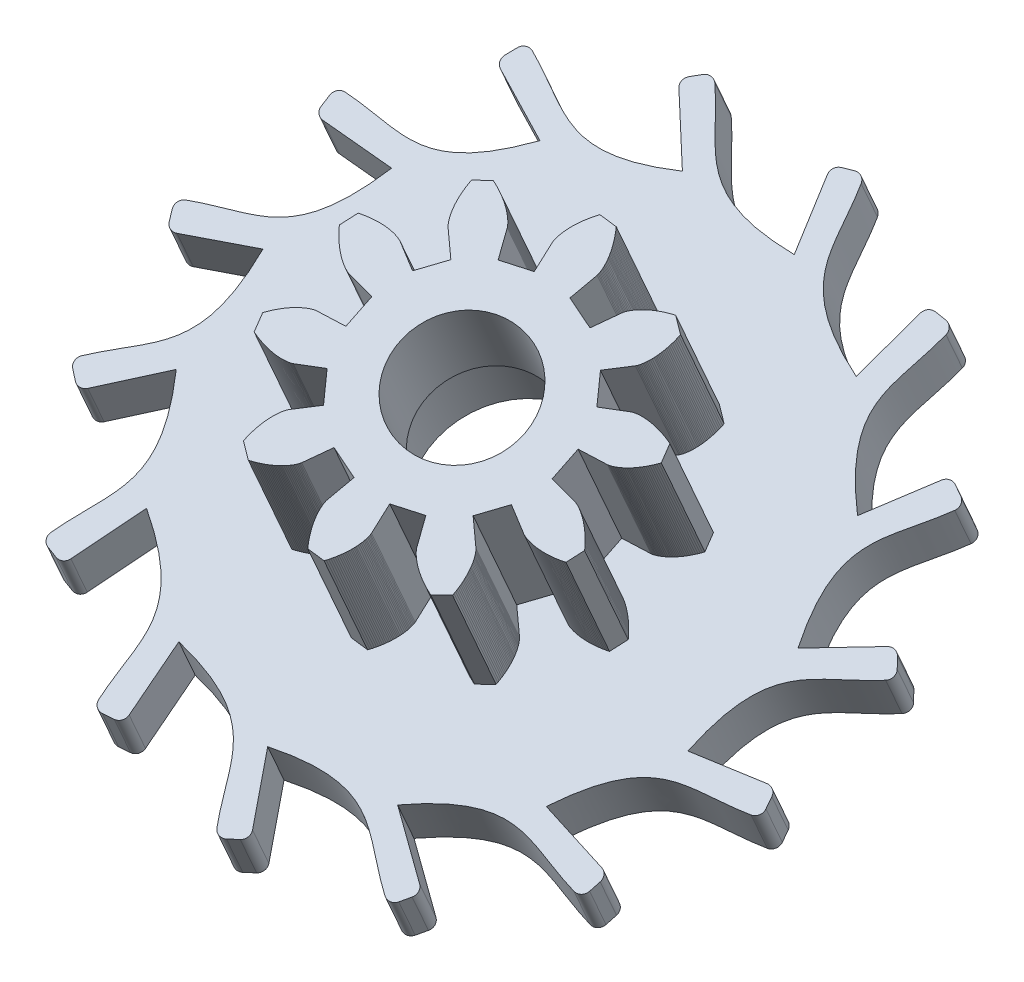
SolidWorks part; units mm, degrees
ref_plane "Plan de face" through (0, 0, 0) normal (0, 0, 1) x (1, 0, 0)
ref_plane "Plan de dessus" through (0, 0, 0) normal (0, 1, 0) x (1, 0, 0)
ref_plane "Plan de droite" through (0, 0, 0) normal (1, 0, 0) x (0, 0, -1)
ref_plane "Plan1" through (6.4076, 24.4468, 14.3554) normal (0.2205, 0.8411, 0.4939) x (-0.9673, 0.2535, 0)
sketch "Esquisse1" plane through (6.4076, 24.4468, 14.3554) normal (0.2205, 0.8411, 0.4939) x (-0.9673, 0.2535, 0)
  line L0 (11.804, -29.6296) -> (11.7288, -30.9131)
  line L1 (11.7288, -30.9131) -> (15.3223, -31.2884)
  line L2 (9.0927, -36.0696) -> (9.5461, -37.2727)
  line L3 (9.5461, -37.2727) -> (12.9816, -36.1539)
  line L4 (9.2353, -43.0555) -> (10.1388, -43.9702)
  line L5 (10.1388, -43.9702) -> (12.8222, -41.5508)
  line L6 (12.207, -49.3796) -> (13.4044, -49.8477)
  line L7 (13.4044, -49.8477) -> (14.8718, -46.546)
  line L8 (17.4939, -53.9481) -> (18.7782, -53.8887)
  line L9 (18.7782, -53.8887) -> (18.7758, -50.2757)
  line L10 (24.182, -55.9713) -> (25.3312, -55.3947)
  line L11 (25.3312, -55.3947) -> (23.8594, -52.095)
  line L12 (31.1148, -55.0993) -> (31.9301, -54.1052)
  line L13 (31.9301, -54.1052) -> (29.2434, -51.6893)
  line L14 (37.0936, -51.4829) -> (37.434, -50.2431)
  line L15 (37.434, -50.2431) -> (33.997, -49.1289)
  line L16 (41.0845, -45.7473) -> (40.8912, -44.4763)
  line L17 (40.8912, -44.4763) -> (37.2981, -44.8563)
  line L18 (42.3975, -38.8844) -> (41.7039, -37.8018)
  line L19 (41.7039, -37.8018) -> (38.5761, -39.6105)
  line L20 (40.8056, -32.0807) -> (39.7317, -31.3739)
  line L21 (39.7317, -31.3739) -> (37.6099, -34.2983)
  line L22 (36.584, -26.5128) -> (35.3154, -26.3038)
  line L23 (35.3154, -26.3038) -> (34.5666, -29.8384)
  line L24 (30.4627, -23.1432) -> (29.2188, -23.4684)
  line L25 (29.2188, -23.4684) -> (29.9724, -27.002)
  line L26 (23.5001, -22.5548) -> (22.496, -23.3577)
  line L27 (22.496, -23.3577) -> (24.6217, -26.2793)
  line L28 (16.9001, -24.8492) -> (16.3094, -25.9911)
  line L29 (16.3094, -25.9911) -> (19.4396, -27.7955)
  spline S0 degree 3 poles (15.3223, -31.2884) (13.6936, -35.7353) (11.8984, -34.9533) (9.0927, -36.0696) knots 0 0 0 0 1 1 1 1
  spline S1 degree 3 poles (12.9816, -36.1539) (13.3024, -40.8788) (11.3444, -40.8946) (9.2353, -43.0555) knots 0 0 0 0 1 1 1 1
  spline S2 degree 3 poles (12.8222, -41.5508) (15.0371, -45.7368) (13.2548, -46.5476) (12.207, -49.3796) knots 0 0 0 0 1 1 1 1
  spline S3 degree 3 poles (14.8718, -46.546) (18.5977, -49.4692) (17.2993, -50.9348) (17.4939, -53.9481) knots 0 0 0 0 1 1 1 1
  spline S4 degree 3 poles (18.7758, -50.2757) (23.3686, -51.4306) (22.7786, -53.2977) (24.182, -55.9713) knots 0 0 0 0 1 1 1 1
  spline S5 degree 3 poles (23.8594, -52.095) (28.5249, -51.2821) (28.7453, -53.2277) (31.1148, -55.0993) knots 0 0 0 0 1 1 1 1
  spline S6 degree 3 poles (29.2434, -51.6893) (33.1749, -49.0491) (34.1676, -50.7368) (37.0936, -51.4829) knots 0 0 0 0 1 1 1 1
  spline S7 degree 3 poles (33.997, -49.1289) (36.5147, -45.1178) (38.108, -46.2558) (41.0845, -45.7473) knots 0 0 0 0 1 1 1 1
  spline S8 degree 3 poles (37.2981, -44.8563) (37.9667, -40.168) (39.8852, -40.5596) (42.3975, -38.8844) knots 0 0 0 0 1 1 1 1
  spline S9 degree 3 poles (38.5761, -39.6105) (37.28, -35.0555) (39.1919, -34.6329) (40.8056, -32.0807) knots 0 0 0 0 1 1 1 1
  spline S10 degree 3 poles (37.6099, -34.2983) (34.5731, -30.6644) (36.1479, -29.5007) (36.584, -26.5128) knots 0 0 0 0 1 1 1 1
  spline S11 degree 3 poles (34.5666, -29.8384) (30.3143, -27.7538) (31.2796, -26.0502) (30.4627, -23.1432) knots 0 0 0 0 1 1 1 1
  spline S12 degree 3 poles (29.9724, -27.002) (25.2398, -26.8271) (25.4287, -24.8782) (23.5001, -22.5548) knots 0 0 0 0 1 1 1 1
  spline S13 degree 3 poles (24.6217, -26.2793) (20.2272, -28.0445) (19.607, -26.1873) (16.9001, -24.8492) knots 0 0 0 0 1 1 1 1
  spline S14 degree 3 poles (19.4396, -27.7955) (16.143, -31.1955) (14.8211, -29.7511) (11.804, -29.6296) knots 0 0 0 0 1 1 1 1
extrude "Boss.-Extru.1" add sketch "Esquisse1" against normal blind 3
sketch "Esquisse2" plane through (6.4076, 24.4468, 14.3554) normal (0.2205, 0.8411, 0.4939) x (-0.9754, 0.1901, 0.1116)
  line L0 (25.2708, -43.1432) -> (26.5155, -43.3845)
  line L1 (26.5155, -43.3845) -> (26.5672, -43.3993)
  line L2 (26.5672, -43.3993) -> (26.6157, -43.4171)
  line L3 (26.6157, -43.4171) -> (26.6676, -43.4388)
  line L4 (26.6676, -43.4388) -> (26.7161, -43.4614)
  line L5 (26.7161, -43.4614) -> (26.7707, -43.4892)
  line L6 (26.7707, -43.4892) -> (26.8153, -43.5137)
  line L7 (26.8153, -43.5137) -> (26.8631, -43.5415)
  line L8 (26.8631, -43.5415) -> (26.9137, -43.5729)
  line L9 (26.9137, -43.5729) -> (26.9671, -43.6079)
  line L10 (26.9671, -43.6079) -> (27.0231, -43.6467)
  line L11 (27.0231, -43.6467) -> (27.0816, -43.6895)
  line L12 (27.0816, -43.6895) -> (27.1423, -43.7365)
  line L13 (27.1423, -43.7365) -> (27.184, -43.7702)
  line L14 (27.184, -43.7702) -> (27.2265, -43.8058)
  line L15 (27.2265, -43.8058) -> (27.2698, -43.8435)
  line L16 (27.2698, -43.8435) -> (27.3139, -43.8832)
  line L17 (27.3139, -43.8832) -> (27.3587, -43.9249)
  line L18 (27.3587, -43.9249) -> (27.4041, -43.9687)
  line L19 (27.4041, -43.9687) -> (27.4502, -44.0147)
  line L20 (27.4502, -44.0147) -> (27.4967, -44.0629)
  line L21 (27.4967, -44.0629) -> (27.5437, -44.1132)
  line L22 (27.5437, -44.1132) -> (27.5911, -44.1658)
  line L23 (27.5911, -44.1658) -> (27.6388, -44.2207)
  line L24 (27.6388, -44.2207) -> (27.6868, -44.2778)
  line L25 (27.6868, -44.2778) -> (27.735, -44.3373)
  line L26 (27.735, -44.3373) -> (27.7833, -44.3991)
  line L27 (27.7833, -44.3991) -> (27.8317, -44.4632)
  line L28 (27.8317, -44.4632) -> (27.8801, -44.5297)
  line L29 (27.8801, -44.5297) -> (27.9284, -44.5987)
  line L30 (27.9284, -44.5987) -> (27.9768, -44.6704)
  line L31 (27.9768, -44.6704) -> (27.6974, -45.4049)
  line L32 (27.6974, -45.4049) -> (27.6135, -45.4263)
  line L33 (27.6135, -45.4263) -> (27.5316, -45.4457)
  line L34 (27.5316, -45.4457) -> (27.4512, -45.4632)
  line L35 (27.4512, -45.4632) -> (27.3724, -45.479)
  line L36 (27.3724, -45.479) -> (27.2953, -45.493)
  line L37 (27.2953, -45.493) -> (27.2197, -45.5054)
  line L38 (27.2197, -45.5054) -> (27.1459, -45.5162)
  line L39 (27.1459, -45.5162) -> (27.0738, -45.5255)
  line L40 (27.0738, -45.5255) -> (27.0034, -45.5333)
  line L41 (27.0034, -45.5333) -> (26.9349, -45.5396)
  line L42 (26.9349, -45.5396) -> (26.8681, -45.5447)
  line L43 (26.8681, -45.5447) -> (26.8031, -45.5484)
  line L44 (26.8031, -45.5484) -> (26.74, -45.551)
  line L45 (26.74, -45.551) -> (26.6788, -45.5524)
  line L46 (26.6788, -45.5524) -> (26.6195, -45.5527)
  line L47 (26.6195, -45.5527) -> (26.5621, -45.552)
  line L48 (26.5621, -45.552) -> (26.5067, -45.5504)
  line L49 (26.5067, -45.5504) -> (26.4532, -45.5479)
  line L50 (26.4532, -45.5479) -> (26.3766, -45.5427)
  line L51 (26.3766, -45.5427) -> (26.3044, -45.5358)
  line L52 (26.3044, -45.5358) -> (26.2368, -45.5276)
  line L53 (26.2368, -45.5276) -> (26.1736, -45.5182)
  line L54 (26.1736, -45.5182) -> (26.1149, -45.508)
  line L55 (26.1149, -45.508) -> (26.0608, -45.497)
  line L56 (26.0608, -45.497) -> (26.0111, -45.4856)
  line L57 (26.0111, -45.4856) -> (25.9519, -45.4701)
  line L58 (25.9519, -45.4701) -> (25.9006, -45.4548)
  line L59 (25.9006, -45.4548) -> (25.8474, -45.4366)
  line L60 (25.8474, -45.4366) -> (25.7994, -45.4175)
  line L61 (25.7994, -45.4175) -> (25.7509, -45.3942)
  line L62 (25.7509, -45.3942) -> (24.6605, -44.7472)
  line L63 (24.6605, -44.7472) -> (23.7699, -45.8537)
  line L64 (23.7699, -45.8537) -> (24.6351, -46.7806)
  line L65 (24.6351, -46.7806) -> (24.6682, -46.823)
  line L66 (24.6682, -46.823) -> (24.697, -46.8658)
  line L67 (24.697, -46.8658) -> (24.7262, -46.9139)
  line L68 (24.7262, -46.9139) -> (24.7521, -46.9607)
  line L69 (24.7521, -46.9607) -> (24.7799, -47.0153)
  line L70 (24.7799, -47.0153) -> (24.8017, -47.0613)
  line L71 (24.8017, -47.0613) -> (24.824, -47.1119)
  line L72 (24.824, -47.1119) -> (24.8465, -47.167)
  line L73 (24.8465, -47.167) -> (24.8692, -47.2267)
  line L74 (24.8692, -47.2267) -> (24.8917, -47.2911)
  line L75 (24.8917, -47.2911) -> (24.9138, -47.3601)
  line L76 (24.9138, -47.3601) -> (24.9353, -47.4338)
  line L77 (24.9353, -47.4338) -> (24.9492, -47.4855)
  line L78 (24.9492, -47.4855) -> (24.9626, -47.5393)
  line L79 (24.9626, -47.5393) -> (24.9755, -47.5953)
  line L80 (24.9755, -47.5953) -> (24.9879, -47.6533)
  line L81 (24.9879, -47.6533) -> (24.9996, -47.7134)
  line L82 (24.9996, -47.7134) -> (25.0106, -47.7756)
  line L83 (25.0106, -47.7756) -> (25.0208, -47.8398)
  line L84 (25.0208, -47.8398) -> (25.0301, -47.9061)
  line L85 (25.0301, -47.9061) -> (25.0386, -47.9745)
  line L86 (25.0386, -47.9745) -> (25.046, -48.0449)
  line L87 (25.046, -48.0449) -> (25.0524, -48.1173)
  line L88 (25.0524, -48.1173) -> (25.0576, -48.1917)
  line L89 (25.0576, -48.1917) -> (25.0616, -48.2682)
  line L90 (25.0616, -48.2682) -> (25.0644, -48.3466)
  line L91 (25.0644, -48.3466) -> (25.0658, -48.4269)
  line L92 (25.0658, -48.4269) -> (25.0659, -48.5092)
  line L93 (25.0659, -48.5092) -> (25.0644, -48.5934)
  line L94 (25.0644, -48.5934) -> (25.0615, -48.6798)
  line L95 (25.0615, -48.6798) -> (24.4037, -49.1098)
  line L96 (24.4037, -49.1098) -> (24.3233, -49.0778)
  line L97 (24.3233, -49.0778) -> (24.2456, -49.0453)
  line L98 (24.2456, -49.0453) -> (24.1703, -49.0123)
  line L99 (24.1703, -49.0123) -> (24.0972, -48.9787)
  line L100 (24.0972, -48.9787) -> (24.0265, -48.9447)
  line L101 (24.0265, -48.9447) -> (23.9582, -48.9104)
  line L102 (23.9582, -48.9104) -> (23.8921, -48.8757)
  line L103 (23.8921, -48.8757) -> (23.8283, -48.8408)
  line L104 (23.8283, -48.8408) -> (23.7668, -48.8058)
  line L105 (23.7668, -48.8058) -> (23.7076, -48.7706)
  line L106 (23.7076, -48.7706) -> (23.6506, -48.7354)
  line L107 (23.6506, -48.7354) -> (23.5958, -48.7003)
  line L108 (23.5958, -48.7003) -> (23.5433, -48.6653)
  line L109 (23.5433, -48.6653) -> (23.4929, -48.6305)
  line L110 (23.4929, -48.6305) -> (23.4448, -48.5959)
  line L111 (23.4448, -48.5959) -> (23.3987, -48.5616)
  line L112 (23.3987, -48.5616) -> (23.3548, -48.5276)
  line L113 (23.3548, -48.5276) -> (23.313, -48.4942)
  line L114 (23.313, -48.4942) -> (23.2541, -48.4449)
  line L115 (23.2541, -48.4449) -> (23.1998, -48.3969)
  line L116 (23.1998, -48.3969) -> (23.1499, -48.3505)
  line L117 (23.1499, -48.3505) -> (23.1043, -48.3058)
  line L118 (23.1043, -48.3058) -> (23.0629, -48.263)
  line L119 (23.0629, -48.263) -> (23.0255, -48.2224)
  line L120 (23.0255, -48.2224) -> (22.992, -48.184)
  line L121 (22.992, -48.184) -> (22.9532, -48.1366)
  line L122 (22.9532, -48.1366) -> (22.9207, -48.094)
  line L123 (22.9207, -48.094) -> (22.8884, -48.048)
  line L124 (22.8884, -48.048) -> (22.8607, -48.0044)
  line L125 (22.8607, -48.0044) -> (22.8352, -47.9571)
  line L126 (22.8352, -47.9571) -> (22.3334, -46.7927)
  line L127 (22.3334, -46.7927) -> (20.9625, -47.1644)
  line L128 (20.9625, -47.1644) -> (21.1176, -48.4228)
  line L129 (21.1176, -48.4228) -> (21.1195, -48.4765)
  line L130 (21.1195, -48.4765) -> (21.1176, -48.5282)
  line L131 (21.1176, -48.5282) -> (21.113, -48.5842)
  line L132 (21.113, -48.5842) -> (21.1064, -48.6373)
  line L133 (21.1064, -48.6373) -> (21.0969, -48.6978)
  line L134 (21.0969, -48.6978) -> (21.0874, -48.7479)
  line L135 (21.0874, -48.7479) -> (21.0757, -48.8018)
  line L136 (21.0757, -48.8018) -> (21.0615, -48.8597)
  line L137 (21.0615, -48.8597) -> (21.0447, -48.9213)
  line L138 (21.0447, -48.9213) -> (21.0251, -48.9866)
  line L139 (21.0251, -48.9866) -> (21.0024, -49.0554)
  line L140 (21.0024, -49.0554) -> (20.9765, -49.1277)
  line L141 (20.9765, -49.1277) -> (20.9574, -49.1777)
  line L142 (20.9574, -49.1777) -> (20.9366, -49.2291)
  line L143 (20.9366, -49.2291) -> (20.9142, -49.282)
  line L144 (20.9142, -49.282) -> (20.8901, -49.3362)
  line L145 (20.8901, -49.3362) -> (20.8642, -49.3917)
  line L146 (20.8642, -49.3917) -> (20.8366, -49.4484)
  line L147 (20.8366, -49.4484) -> (20.8071, -49.5064)
  line L148 (20.8071, -49.5064) -> (20.7756, -49.5656)
  line L149 (20.7756, -49.5656) -> (20.7423, -49.6258)
  line L150 (20.7423, -49.6258) -> (20.7069, -49.6871)
  line L151 (20.7069, -49.6871) -> (20.6695, -49.7495)
  line L152 (20.6695, -49.7495) -> (20.63, -49.8128)
  line L153 (20.63, -49.8128) -> (20.5883, -49.877)
  line L154 (20.5883, -49.877) -> (20.5445, -49.942)
  line L155 (20.5445, -49.942) -> (20.4984, -50.0079)
  line L156 (20.4984, -50.0079) -> (20.4501, -50.0745)
  line L157 (20.4501, -50.0745) -> (20.3994, -50.1417)
  line L158 (20.3994, -50.1417) -> (20.3462, -50.2099)
  line L159 (20.3462, -50.2099) -> (19.5613, -50.1711)
  line L160 (19.5613, -50.1711) -> (19.5151, -50.098)
  line L161 (19.5151, -50.098) -> (19.4713, -50.0261)
  line L162 (19.4713, -50.0261) -> (19.4298, -49.9551)
  line L163 (19.4298, -49.9551) -> (19.3904, -49.885)
  line L164 (19.3904, -49.885) -> (19.3532, -49.8159)
  line L165 (19.3532, -49.8159) -> (19.3181, -49.7479)
  line L166 (19.3181, -49.7479) -> (19.285, -49.6811)
  line L167 (19.285, -49.6811) -> (19.2539, -49.6153)
  line L168 (19.2539, -49.6153) -> (19.2248, -49.5508)
  line L169 (19.2248, -49.5508) -> (19.1975, -49.4876)
  line L170 (19.1975, -49.4876) -> (19.1721, -49.4256)
  line L171 (19.1721, -49.4256) -> (19.1484, -49.365)
  line L172 (19.1484, -49.365) -> (19.1265, -49.3058)
  line L173 (19.1265, -49.3058) -> (19.1063, -49.248)
  line L174 (19.1063, -49.248) -> (19.0876, -49.1917)
  line L175 (19.0876, -49.1917) -> (19.0705, -49.1369)
  line L176 (19.0705, -49.1369) -> (19.055, -49.0837)
  line L177 (19.055, -49.0837) -> (19.0408, -49.032)
  line L178 (19.0408, -49.032) -> (19.0221, -48.9575)
  line L179 (19.0221, -48.9575) -> (19.0064, -48.8868)
  line L180 (19.0064, -48.8868) -> (18.9933, -48.8199)
  line L181 (18.9933, -48.8199) -> (18.9827, -48.7569)
  line L182 (18.9827, -48.7569) -> (18.9743, -48.698)
  line L183 (18.9743, -48.698) -> (18.968, -48.6431)
  line L184 (18.968, -48.6431) -> (18.9635, -48.5924)
  line L185 (18.9635, -48.5924) -> (18.9599, -48.5312)
  line L186 (18.9599, -48.5312) -> (18.9586, -48.4777)
  line L187 (18.9586, -48.4777) -> (18.9595, -48.4215)
  line L188 (18.9595, -48.4215) -> (18.9628, -48.3699)
  line L189 (18.9628, -48.3699) -> (18.97, -48.3166)
  line L190 (18.97, -48.3166) -> (19.2484, -47.0796)
  line L191 (19.2484, -47.0796) -> (17.9208, -46.5746)
  line L192 (17.9208, -46.5746) -> (17.3066, -47.6838)
  line L193 (17.3066, -47.6838) -> (17.2766, -47.7284)
  line L194 (17.2766, -47.7284) -> (17.2447, -47.7691)
  line L195 (17.2447, -47.7691) -> (17.208, -47.8116)
  line L196 (17.208, -47.8116) -> (17.1715, -47.8508)
  line L197 (17.1715, -47.8508) -> (17.1282, -47.8941)
  line L198 (17.1282, -47.8941) -> (17.0911, -47.929)
  line L199 (17.0911, -47.929) -> (17.0499, -47.9658)
  line L200 (17.0499, -47.9658) -> (17.0045, -48.0043)
  line L201 (17.0045, -48.0043) -> (16.9547, -48.0443)
  line L202 (16.9547, -48.0443) -> (16.9004, -48.0856)
  line L203 (16.9004, -48.0856) -> (16.8416, -48.1279)
  line L204 (16.8416, -48.1279) -> (16.7782, -48.1712)
  line L205 (16.7782, -48.1712) -> (16.7333, -48.2004)
  line L206 (16.7333, -48.2004) -> (16.6862, -48.2298)
  line L207 (16.6862, -48.2298) -> (16.637, -48.2594)
  line L208 (16.637, -48.2594) -> (16.5857, -48.289)
  line L209 (16.5857, -48.289) -> (16.5322, -48.3188)
  line L210 (16.5322, -48.3188) -> (16.4764, -48.3484)
  line L211 (16.4764, -48.3484) -> (16.4185, -48.378)
  line L212 (16.4185, -48.378) -> (16.3583, -48.4074)
  line L213 (16.3583, -48.4074) -> (16.2959, -48.4365)
  line L214 (16.2959, -48.4365) -> (16.2312, -48.4653)
  line L215 (16.2312, -48.4653) -> (16.1643, -48.4937)
  line L216 (16.1643, -48.4937) -> (16.0951, -48.5217)
  line L217 (16.0951, -48.5217) -> (16.0237, -48.5492)
  line L218 (16.0237, -48.5492) -> (15.95, -48.576)
  line L219 (15.95, -48.576) -> (15.874, -48.6022)
  line L220 (15.874, -48.6022) -> (15.7958, -48.6277)
  line L221 (15.7958, -48.6277) -> (15.7153, -48.6523)
  line L222 (15.7153, -48.6523) -> (15.6321, -48.6762)
  line L223 (15.6321, -48.6762) -> (15.02, -48.1835)
  line L224 (15.02, -48.1835) -> (15.0255, -48.0972)
  line L225 (15.0255, -48.0972) -> (15.0324, -48.0133)
  line L226 (15.0324, -48.0133) -> (15.0405, -47.9314)
  line L227 (15.0405, -47.9314) -> (15.0499, -47.8516)
  line L228 (15.0499, -47.8516) -> (15.0604, -47.7738)
  line L229 (15.0604, -47.7738) -> (15.0719, -47.6982)
  line L230 (15.0719, -47.6982) -> (15.0845, -47.6246)
  line L231 (15.0845, -47.6246) -> (15.098, -47.5532)
  line L232 (15.098, -47.5532) -> (15.1123, -47.4839)
  line L233 (15.1123, -47.4839) -> (15.1274, -47.4167)
  line L234 (15.1274, -47.4167) -> (15.1433, -47.3516)
  line L235 (15.1433, -47.3516) -> (15.1597, -47.2887)
  line L236 (15.1597, -47.2887) -> (15.1768, -47.2279)
  line L237 (15.1768, -47.2279) -> (15.1944, -47.1692)
  line L238 (15.1944, -47.1692) -> (15.2124, -47.1127)
  line L239 (15.2124, -47.1127) -> (15.2308, -47.0583)
  line L240 (15.2308, -47.0583) -> (15.2495, -47.0061)
  line L241 (15.2495, -47.0061) -> (15.2684, -46.956)
  line L242 (15.2684, -46.956) -> (15.2971, -46.8848)
  line L243 (15.2971, -46.8848) -> (15.3259, -46.8183)
  line L244 (15.3259, -46.8183) -> (15.3546, -46.7565)
  line L245 (15.3546, -46.7565) -> (15.383, -46.6993)
  line L246 (15.383, -46.6993) -> (15.4109, -46.6467)
  line L247 (15.4109, -46.6467) -> (15.4381, -46.5985)
  line L248 (15.4381, -46.5985) -> (15.4642, -46.5548)
  line L249 (15.4642, -46.5548) -> (15.4973, -46.5033)
  line L250 (15.4973, -46.5033) -> (15.5277, -46.4592)
  line L251 (15.5277, -46.4592) -> (15.5615, -46.4143)
  line L252 (15.5615, -46.4143) -> (15.5944, -46.3745)
  line L253 (15.5944, -46.3745) -> (15.6316, -46.3356)
  line L254 (15.6316, -46.3356) -> (16.5839, -45.4985)
  line L255 (16.5839, -45.4985) -> (15.8068, -44.3096)
  line L256 (15.8068, -44.3096) -> (14.6579, -44.8459)
  line L257 (14.6579, -44.8459) -> (14.6073, -44.8644)
  line L258 (14.6073, -44.8644) -> (14.5577, -44.8786)
  line L259 (14.5577, -44.8786) -> (14.503, -44.8914)
  line L260 (14.503, -44.8914) -> (14.4504, -44.9016)
  line L261 (14.4504, -44.9016) -> (14.3899, -44.9112)
  line L262 (14.3899, -44.9112) -> (14.3394, -44.9177)
  line L263 (14.3394, -44.9177) -> (14.2844, -44.9232)
  line L264 (14.2844, -44.9232) -> (14.225, -44.9276)
  line L265 (14.225, -44.9276) -> (14.1612, -44.9307)
  line L266 (14.1612, -44.9307) -> (14.0931, -44.9322)
  line L267 (14.0931, -44.9322) -> (14.0206, -44.9319)
  line L268 (14.0206, -44.9319) -> (13.9439, -44.9296)
  line L269 (13.9439, -44.9296) -> (13.8904, -44.9268)
  line L270 (13.8904, -44.9268) -> (13.835, -44.923)
  line L271 (13.835, -44.923) -> (13.7779, -44.918)
  line L272 (13.7779, -44.918) -> (13.7189, -44.9118)
  line L273 (13.7189, -44.9118) -> (13.6581, -44.9044)
  line L274 (13.6581, -44.9044) -> (13.5956, -44.8956)
  line L275 (13.5956, -44.8956) -> (13.5313, -44.8855)
  line L276 (13.5313, -44.8855) -> (13.4654, -44.8739)
  line L277 (13.4654, -44.8739) -> (13.3977, -44.8608)
  line L278 (13.3977, -44.8608) -> (13.3285, -44.8461)
  line L279 (13.3285, -44.8461) -> (13.2576, -44.8298)
  line L280 (13.2576, -44.8298) -> (13.1852, -44.8117)
  line L281 (13.1852, -44.8117) -> (13.1113, -44.792)
  line L282 (13.1113, -44.792) -> (13.0359, -44.7704)
  line L283 (13.0359, -44.7704) -> (12.959, -44.7469)
  line L284 (12.959, -44.7469) -> (12.8808, -44.7215)
  line L285 (12.8808, -44.7215) -> (12.8012, -44.6941)
  line L286 (12.8012, -44.6941) -> (12.7199, -44.6646)
  line L287 (12.7199, -44.6646) -> (12.5142, -43.9061)
  line L288 (12.5142, -43.9061) -> (12.5694, -43.8395)
  line L289 (12.5694, -43.8395) -> (12.6243, -43.7757)
  line L290 (12.6243, -43.7757) -> (12.679, -43.7143)
  line L291 (12.679, -43.7143) -> (12.7335, -43.6552)
  line L292 (12.7335, -43.6552) -> (12.7877, -43.5985)
  line L293 (12.7877, -43.5985) -> (12.8415, -43.544)
  line L294 (12.8415, -43.544) -> (12.8949, -43.4919)
  line L295 (12.8949, -43.4919) -> (12.9478, -43.442)
  line L296 (12.9478, -43.442) -> (13.0001, -43.3944)
  line L297 (13.0001, -43.3944) -> (13.0519, -43.3489)
  line L298 (13.0519, -43.3489) -> (13.1029, -43.3056)
  line L299 (13.1029, -43.3056) -> (13.1533, -43.2644)
  line L300 (13.1533, -43.2644) -> (13.2028, -43.2252)
  line L301 (13.2028, -43.2252) -> (13.2515, -43.1881)
  line L302 (13.2515, -43.1881) -> (13.2993, -43.153)
  line L303 (13.2993, -43.153) -> (13.3461, -43.1198)
  line L304 (13.3461, -43.1198) -> (13.3919, -43.0885)
  line L305 (13.3919, -43.0885) -> (13.4367, -43.0591)
  line L306 (13.4367, -43.0591) -> (13.5018, -43.0183)
  line L307 (13.5018, -43.0183) -> (13.5642, -42.9815)
  line L308 (13.5642, -42.9815) -> (13.6237, -42.9483)
  line L309 (13.6237, -42.9483) -> (13.6803, -42.9188)
  line L310 (13.6803, -42.9188) -> (13.7338, -42.8926)
  line L311 (13.7338, -42.8926) -> (13.7841, -42.8696)
  line L312 (13.7841, -42.8696) -> (13.8309, -42.8497)
  line L313 (13.8309, -42.8497) -> (13.888, -42.8274)
  line L314 (13.888, -42.8274) -> (13.9385, -42.8096)
  line L315 (13.9385, -42.8096) -> (13.9922, -42.7931)
  line L316 (13.9922, -42.7931) -> (14.0422, -42.7803)
  line L317 (14.0422, -42.7803) -> (14.0952, -42.7706)
  line L318 (14.0952, -42.7706) -> (15.3577, -42.6532)
  line L319 (15.3577, -42.6532) -> (15.4278, -41.2345)
  line L320 (15.4278, -41.2345) -> (14.183, -40.9932)
  line L321 (14.183, -40.9932) -> (14.1313, -40.9784)
  line L322 (14.1313, -40.9784) -> (14.0828, -40.9606)
  line L323 (14.0828, -40.9606) -> (14.031, -40.9389)
  line L324 (14.031, -40.9389) -> (13.9824, -40.9163)
  line L325 (13.9824, -40.9163) -> (13.9279, -40.8885)
  line L326 (13.9279, -40.8885) -> (13.8832, -40.864)
  line L327 (13.8832, -40.864) -> (13.8355, -40.8362)
  line L328 (13.8355, -40.8362) -> (13.7848, -40.8048)
  line L329 (13.7848, -40.8048) -> (13.7314, -40.7698)
  line L330 (13.7314, -40.7698) -> (13.6754, -40.731)
  line L331 (13.6754, -40.731) -> (13.6169, -40.6882)
  line L332 (13.6169, -40.6882) -> (13.5562, -40.6412)
  line L333 (13.5562, -40.6412) -> (13.5146, -40.6075)
  line L334 (13.5146, -40.6075) -> (13.4721, -40.5719)
  line L335 (13.4721, -40.5719) -> (13.4287, -40.5342)
  line L336 (13.4287, -40.5342) -> (13.3846, -40.4945)
  line L337 (13.3846, -40.4945) -> (13.3398, -40.4528)
  line L338 (13.3398, -40.4528) -> (13.2944, -40.409)
  line L339 (13.2944, -40.409) -> (13.2484, -40.363)
  line L340 (13.2484, -40.363) -> (13.2018, -40.3148)
  line L341 (13.2018, -40.3148) -> (13.1548, -40.2645)
  line L342 (13.1548, -40.2645) -> (13.1075, -40.2119)
  line L343 (13.1075, -40.2119) -> (13.0597, -40.157)
  line L344 (13.0597, -40.157) -> (13.0117, -40.0999)
  line L345 (13.0117, -40.0999) -> (12.9636, -40.0404)
  line L346 (12.9636, -40.0404) -> (12.9152, -39.9786)
  line L347 (12.9152, -39.9786) -> (12.8668, -39.9145)
  line L348 (12.8668, -39.9145) -> (12.8185, -39.8479)
  line L349 (12.8185, -39.8479) -> (12.7701, -39.779)
  line L350 (12.7701, -39.779) -> (12.7217, -39.7073)
  line L351 (12.7217, -39.7073) -> (13.0012, -38.9728)
  line L352 (13.0012, -38.9728) -> (13.085, -38.9514)
  line L353 (13.085, -38.9514) -> (13.1669, -38.932)
  line L354 (13.1669, -38.932) -> (13.2473, -38.9145)
  line L355 (13.2473, -38.9145) -> (13.3261, -38.8987)
  line L356 (13.3261, -38.8987) -> (13.4033, -38.8847)
  line L357 (13.4033, -38.8847) -> (13.4788, -38.8723)
  line L358 (13.4788, -38.8723) -> (13.5526, -38.8615)
  line L359 (13.5526, -38.8615) -> (13.6247, -38.8522)
  line L360 (13.6247, -38.8522) -> (13.6951, -38.8444)
  line L361 (13.6951, -38.8444) -> (13.7637, -38.8381)
  line L362 (13.7637, -38.8381) -> (13.8305, -38.833)
  line L363 (13.8305, -38.833) -> (13.8954, -38.8292)
  line L364 (13.8954, -38.8292) -> (13.9585, -38.8267)
  line L365 (13.9585, -38.8267) -> (14.0197, -38.8253)
  line L366 (14.0197, -38.8253) -> (14.079, -38.825)
  line L367 (14.079, -38.825) -> (14.1364, -38.8256)
  line L368 (14.1364, -38.8256) -> (14.1919, -38.8273)
  line L369 (14.1919, -38.8273) -> (14.2454, -38.8298)
  line L370 (14.2454, -38.8298) -> (14.322, -38.835)
  line L371 (14.322, -38.835) -> (14.3941, -38.8419)
  line L372 (14.3941, -38.8419) -> (14.4618, -38.8501)
  line L373 (14.4618, -38.8501) -> (14.5249, -38.8595)
  line L374 (14.5249, -38.8595) -> (14.5836, -38.8697)
  line L375 (14.5836, -38.8697) -> (14.6378, -38.8807)
  line L376 (14.6378, -38.8807) -> (14.6874, -38.8921)
  line L377 (14.6874, -38.8921) -> (14.7466, -38.9076)
  line L378 (14.7466, -38.9076) -> (14.798, -38.9229)
  line L379 (14.798, -38.9229) -> (14.8511, -38.9411)
  line L380 (14.8511, -38.9411) -> (14.8992, -38.9601)
  line L381 (14.8992, -38.9601) -> (14.9476, -38.9835)
  line L382 (14.9476, -38.9835) -> (16.038, -39.6305)
  line L383 (16.038, -39.6305) -> (16.9286, -38.524)
  line L384 (16.9286, -38.524) -> (16.0635, -37.5971)
  line L385 (16.0635, -37.5971) -> (16.0303, -37.5547)
  line L386 (16.0303, -37.5547) -> (16.0015, -37.5119)
  line L387 (16.0015, -37.5119) -> (15.9724, -37.4638)
  line L388 (15.9724, -37.4638) -> (15.9464, -37.417)
  line L389 (15.9464, -37.417) -> (15.9186, -37.3624)
  line L390 (15.9186, -37.3624) -> (15.8968, -37.3163)
  line L391 (15.8968, -37.3163) -> (15.8746, -37.2658)
  line L392 (15.8746, -37.2658) -> (15.852, -37.2107)
  line L393 (15.852, -37.2107) -> (15.8294, -37.151)
  line L394 (15.8294, -37.151) -> (15.8069, -37.0866)
  line L395 (15.8069, -37.0866) -> (15.7848, -37.0176)
  line L396 (15.7848, -37.0176) -> (15.7633, -36.9439)
  line L397 (15.7633, -36.9439) -> (15.7494, -36.8922)
  line L398 (15.7494, -36.8922) -> (15.7359, -36.8383)
  line L399 (15.7359, -36.8383) -> (15.723, -36.7824)
  line L400 (15.723, -36.7824) -> (15.7106, -36.7244)
  line L401 (15.7106, -36.7244) -> (15.6989, -36.6643)
  line L402 (15.6989, -36.6643) -> (15.6879, -36.6021)
  line L403 (15.6879, -36.6021) -> (15.6777, -36.5379)
  line L404 (15.6777, -36.5379) -> (15.6684, -36.4716)
  line L405 (15.6684, -36.4716) -> (15.66, -36.4032)
  line L406 (15.66, -36.4032) -> (15.6525, -36.3328)
  line L407 (15.6525, -36.3328) -> (15.6462, -36.2604)
  line L408 (15.6462, -36.2604) -> (15.6409, -36.186)
  line L409 (15.6409, -36.186) -> (15.6369, -36.1095)
  line L410 (15.6369, -36.1095) -> (15.6341, -36.0311)
  line L411 (15.6341, -36.0311) -> (15.6327, -35.9508)
  line L412 (15.6327, -35.9508) -> (15.6327, -35.8685)
  line L413 (15.6327, -35.8685) -> (15.6341, -35.7843)
  line L414 (15.6341, -35.7843) -> (15.6371, -35.6979)
  line L415 (15.6371, -35.6979) -> (16.2949, -35.2679)
  line L416 (16.2949, -35.2679) -> (16.3753, -35.2999)
  line L417 (16.3753, -35.2999) -> (16.4529, -35.3324)
  line L418 (16.4529, -35.3324) -> (16.5283, -35.3654)
  line L419 (16.5283, -35.3654) -> (16.6013, -35.399)
  line L420 (16.6013, -35.399) -> (16.672, -35.433)
  line L421 (16.672, -35.433) -> (16.7404, -35.4673)
  line L422 (16.7404, -35.4673) -> (16.8064, -35.502)
  line L423 (16.8064, -35.502) -> (16.8702, -35.5369)
  line L424 (16.8702, -35.5369) -> (16.9317, -35.5719)
  line L425 (16.9317, -35.5719) -> (16.991, -35.6071)
  line L426 (16.991, -35.6071) -> (17.048, -35.6423)
  line L427 (17.048, -35.6423) -> (17.1027, -35.6774)
  line L428 (17.1027, -35.6774) -> (17.1553, -35.7124)
  line L429 (17.1553, -35.7124) -> (17.2056, -35.7472)
  line L430 (17.2056, -35.7472) -> (17.2538, -35.7818)
  line L431 (17.2538, -35.7818) -> (17.2998, -35.8161)
  line L432 (17.2998, -35.8161) -> (17.3437, -35.85)
  line L433 (17.3437, -35.85) -> (17.3855, -35.8835)
  line L434 (17.3855, -35.8835) -> (17.4444, -35.9328)
  line L435 (17.4444, -35.9328) -> (17.4987, -35.9808)
  line L436 (17.4987, -35.9808) -> (17.5487, -36.0272)
  line L437 (17.5487, -36.0272) -> (17.5943, -36.0719)
  line L438 (17.5943, -36.0719) -> (17.6357, -36.1147)
  line L439 (17.6357, -36.1147) -> (17.6731, -36.1553)
  line L440 (17.6731, -36.1553) -> (17.7065, -36.1937)
  line L441 (17.7065, -36.1937) -> (17.7453, -36.2411)
  line L442 (17.7453, -36.2411) -> (17.7778, -36.2837)
  line L443 (17.7778, -36.2837) -> (17.8101, -36.3297)
  line L444 (17.8101, -36.3297) -> (17.8378, -36.3733)
  line L445 (17.8378, -36.3733) -> (17.8633, -36.4206)
  line L446 (17.8633, -36.4206) -> (18.3652, -37.585)
  line L447 (18.3652, -37.585) -> (19.7361, -37.2133)
  line L448 (19.7361, -37.2133) -> (19.581, -35.9549)
  line L449 (19.581, -35.9549) -> (19.5791, -35.9012)
  line L450 (19.5791, -35.9012) -> (19.5809, -35.8495)
  line L451 (19.5809, -35.8495) -> (19.5856, -35.7935)
  line L452 (19.5856, -35.7935) -> (19.5921, -35.7404)
  line L453 (19.5921, -35.7404) -> (19.6017, -35.6799)
  line L454 (19.6017, -35.6799) -> (19.6112, -35.6298)
  line L455 (19.6112, -35.6298) -> (19.6229, -35.5759)
  line L456 (19.6229, -35.5759) -> (19.637, -35.518)
  line L457 (19.637, -35.518) -> (19.6538, -35.4564)
  line L458 (19.6538, -35.4564) -> (19.6734, -35.3911)
  line L459 (19.6734, -35.3911) -> (19.6961, -35.3223)
  line L460 (19.6961, -35.3223) -> (19.722, -35.25)
  line L461 (19.722, -35.25) -> (19.7412, -35.2)
  line L462 (19.7412, -35.2) -> (19.7619, -35.1486)
  line L463 (19.7619, -35.1486) -> (19.7844, -35.0957)
  line L464 (19.7844, -35.0957) -> (19.8085, -35.0415)
  line L465 (19.8085, -35.0415) -> (19.8343, -34.986)
  line L466 (19.8343, -34.986) -> (19.862, -34.9293)
  line L467 (19.862, -34.9293) -> (19.8915, -34.8713)
  line L468 (19.8915, -34.8713) -> (19.9229, -34.8121)
  line L469 (19.9229, -34.8121) -> (19.9563, -34.7519)
  line L470 (19.9563, -34.7519) -> (19.9916, -34.6906)
  line L471 (19.9916, -34.6906) -> (20.029, -34.6282)
  line L472 (20.029, -34.6282) -> (20.0686, -34.5649)
  line L473 (20.0686, -34.5649) -> (20.1102, -34.5007)
  line L474 (20.1102, -34.5007) -> (20.1541, -34.4357)
  line L475 (20.1541, -34.4357) -> (20.2001, -34.3698)
  line L476 (20.2001, -34.3698) -> (20.2485, -34.3032)
  line L477 (20.2485, -34.3032) -> (20.2991, -34.236)
  line L478 (20.2991, -34.236) -> (20.3523, -34.1678)
  line L479 (20.3523, -34.1678) -> (21.1372, -34.2066)
  line L480 (21.1372, -34.2066) -> (21.1835, -34.2797)
  line L481 (21.1835, -34.2797) -> (21.2272, -34.3516)
  line L482 (21.2272, -34.3516) -> (21.2687, -34.4226)
  line L483 (21.2687, -34.4226) -> (21.3081, -34.4927)
  line L484 (21.3081, -34.4927) -> (21.3453, -34.5618)
  line L485 (21.3453, -34.5618) -> (21.3804, -34.6298)
  line L486 (21.3804, -34.6298) -> (21.4135, -34.6966)
  line L487 (21.4135, -34.6966) -> (21.4446, -34.7624)
  line L488 (21.4446, -34.7624) -> (21.4737, -34.8269)
  line L489 (21.4737, -34.8269) -> (21.501, -34.8901)
  line L490 (21.501, -34.8901) -> (21.5264, -34.9521)
  line L491 (21.5264, -34.9521) -> (21.5501, -35.0127)
  line L492 (21.5501, -35.0127) -> (21.572, -35.0719)
  line L493 (21.572, -35.0719) -> (21.5923, -35.1297)
  line L494 (21.5923, -35.1297) -> (21.6109, -35.186)
  line L495 (21.6109, -35.186) -> (21.628, -35.2408)
  line L496 (21.628, -35.2408) -> (21.6436, -35.294)
  line L497 (21.6436, -35.294) -> (21.6577, -35.3457)
  line L498 (21.6577, -35.3457) -> (21.6764, -35.4202)
  line L499 (21.6764, -35.4202) -> (21.6922, -35.4909)
  line L500 (21.6922, -35.4909) -> (21.7053, -35.5578)
  line L501 (21.7053, -35.5578) -> (21.7159, -35.6208)
  line L502 (21.7159, -35.6208) -> (21.7242, -35.6797)
  line L503 (21.7242, -35.6797) -> (21.7306, -35.7346)
  line L504 (21.7306, -35.7346) -> (21.7351, -35.7853)
  line L505 (21.7351, -35.7853) -> (21.7386, -35.8465)
  line L506 (21.7386, -35.8465) -> (21.7399, -35.9)
  line L507 (21.7399, -35.9) -> (21.739, -35.9562)
  line L508 (21.739, -35.9562) -> (21.7358, -36.0078)
  line L509 (21.7358, -36.0078) -> (21.7286, -36.0611)
  line L510 (21.7286, -36.0611) -> (21.4501, -37.2981)
  line L511 (21.4501, -37.2981) -> (22.7777, -37.8031)
  line L512 (22.7777, -37.8031) -> (23.3919, -36.6939)
  line L513 (23.3919, -36.6939) -> (23.422, -36.6493)
  line L514 (23.422, -36.6493) -> (23.4538, -36.6086)
  line L515 (23.4538, -36.6086) -> (23.4905, -36.5661)
  line L516 (23.4905, -36.5661) -> (23.527, -36.5269)
  line L517 (23.527, -36.5269) -> (23.5703, -36.4836)
  line L518 (23.5703, -36.4836) -> (23.6074, -36.4487)
  line L519 (23.6074, -36.4487) -> (23.6486, -36.4119)
  line L520 (23.6486, -36.4119) -> (23.6941, -36.3734)
  line L521 (23.6941, -36.3734) -> (23.7439, -36.3334)
  line L522 (23.7439, -36.3334) -> (23.7981, -36.2921)
  line L523 (23.7981, -36.2921) -> (23.8569, -36.2498)
  line L524 (23.8569, -36.2498) -> (23.9203, -36.2065)
  line L525 (23.9203, -36.2065) -> (23.9653, -36.1773)
  line L526 (23.9653, -36.1773) -> (24.0123, -36.1479)
  line L527 (24.0123, -36.1479) -> (24.0615, -36.1183)
  line L528 (24.0615, -36.1183) -> (24.1128, -36.0886)
  line L529 (24.1128, -36.0886) -> (24.1664, -36.0589)
  line L530 (24.1664, -36.0589) -> (24.2221, -36.0293)
  line L531 (24.2221, -36.0293) -> (24.2801, -35.9997)
  line L532 (24.2801, -35.9997) -> (24.3402, -35.9703)
  line L533 (24.3402, -35.9703) -> (24.4027, -35.9412)
  line L534 (24.4027, -35.9412) -> (24.4673, -35.9124)
  line L535 (24.4673, -35.9124) -> (24.5342, -35.8839)
  line L536 (24.5342, -35.8839) -> (24.6034, -35.856)
  line L537 (24.6034, -35.856) -> (24.6748, -35.8285)
  line L538 (24.6748, -35.8285) -> (24.7485, -35.8017)
  line L539 (24.7485, -35.8017) -> (24.8245, -35.7755)
  line L540 (24.8245, -35.7755) -> (24.9028, -35.75)
  line L541 (24.9028, -35.75) -> (24.9832, -35.7254)
  line L542 (24.9832, -35.7254) -> (25.0664, -35.7015)
  line L543 (25.0664, -35.7015) -> (25.6786, -36.1942)
  line L544 (25.6786, -36.1942) -> (25.673, -36.2805)
  line L545 (25.673, -36.2805) -> (25.6662, -36.3644)
  line L546 (25.6662, -36.3644) -> (25.658, -36.4463)
  line L547 (25.658, -36.4463) -> (25.6487, -36.5261)
  line L548 (25.6487, -36.5261) -> (25.6382, -36.6039)
  line L549 (25.6382, -36.6039) -> (25.6266, -36.6795)
  line L550 (25.6266, -36.6795) -> (25.6141, -36.7531)
  line L551 (25.6141, -36.7531) -> (25.6006, -36.8245)
  line L552 (25.6006, -36.8245) -> (25.5863, -36.8939)
  line L553 (25.5863, -36.8939) -> (25.5711, -36.9611)
  line L554 (25.5711, -36.9611) -> (25.5553, -37.0261)
  line L555 (25.5553, -37.0261) -> (25.5388, -37.089)
  line L556 (25.5388, -37.089) -> (25.5217, -37.1498)
  line L557 (25.5217, -37.1498) -> (25.5042, -37.2085)
  line L558 (25.5042, -37.2085) -> (25.4861, -37.265)
  line L559 (25.4861, -37.265) -> (25.4678, -37.3194)
  line L560 (25.4678, -37.3194) -> (25.4491, -37.3716)
  line L561 (25.4491, -37.3716) -> (25.4301, -37.4217)
  line L562 (25.4301, -37.4217) -> (25.4015, -37.4929)
  line L563 (25.4015, -37.4929) -> (25.3727, -37.5594)
  line L564 (25.3727, -37.5594) -> (25.3439, -37.6212)
  line L565 (25.3439, -37.6212) -> (25.3155, -37.6784)
  line L566 (25.3155, -37.6784) -> (25.2876, -37.731)
  line L567 (25.2876, -37.731) -> (25.2605, -37.7792)
  line L568 (25.2605, -37.7792) -> (25.2343, -37.8229)
  line L569 (25.2343, -37.8229) -> (25.2013, -37.8744)
  line L570 (25.2013, -37.8744) -> (25.1708, -37.9185)
  line L571 (25.1708, -37.9185) -> (25.1371, -37.9634)
  line L572 (25.1371, -37.9634) -> (25.1041, -38.0032)
  line L573 (25.1041, -38.0032) -> (25.067, -38.0421)
  line L574 (25.067, -38.0421) -> (24.1146, -38.8792)
  line L575 (24.1146, -38.8792) -> (24.8918, -40.0681)
  line L576 (24.8918, -40.0681) -> (26.0407, -39.5318)
  line L577 (26.0407, -39.5318) -> (26.0912, -39.5133)
  line L578 (26.0912, -39.5133) -> (26.1409, -39.4991)
  line L579 (26.1409, -39.4991) -> (26.1956, -39.4863)
  line L580 (26.1956, -39.4863) -> (26.2482, -39.4761)
  line L581 (26.2482, -39.4761) -> (26.3086, -39.4665)
  line L582 (26.3086, -39.4665) -> (26.3592, -39.46)
  line L583 (26.3592, -39.46) -> (26.4141, -39.4545)
  line L584 (26.4141, -39.4545) -> (26.4735, -39.45)
  line L585 (26.4735, -39.45) -> (26.5373, -39.447)
  line L586 (26.5373, -39.447) -> (26.6054, -39.4455)
  line L587 (26.6054, -39.4455) -> (26.6779, -39.4457)
  line L588 (26.6779, -39.4457) -> (26.7546, -39.4481)
  line L589 (26.7546, -39.4481) -> (26.8081, -39.4509)
  line L590 (26.8081, -39.4509) -> (26.8635, -39.4547)
  line L591 (26.8635, -39.4547) -> (26.9207, -39.4597)
  line L592 (26.9207, -39.4597) -> (26.9797, -39.4659)
  line L593 (26.9797, -39.4659) -> (27.0404, -39.4733)
  line L594 (27.0404, -39.4733) -> (27.103, -39.4821)
  line L595 (27.103, -39.4821) -> (27.1672, -39.4922)
  line L596 (27.1672, -39.4922) -> (27.2332, -39.5038)
  line L597 (27.2332, -39.5038) -> (27.3008, -39.5169)
  line L598 (27.3008, -39.5169) -> (27.3701, -39.5316)
  line L599 (27.3701, -39.5316) -> (27.4409, -39.5479)
  line L600 (27.4409, -39.5479) -> (27.5133, -39.566)
  line L601 (27.5133, -39.566) -> (27.5872, -39.5857)
  line L602 (27.5872, -39.5857) -> (27.6627, -39.6073)
  line L603 (27.6627, -39.6073) -> (27.7395, -39.6308)
  line L604 (27.7395, -39.6308) -> (27.8178, -39.6562)
  line L605 (27.8178, -39.6562) -> (27.8974, -39.6836)
  line L606 (27.8974, -39.6836) -> (27.9787, -39.7131)
  line L607 (27.9787, -39.7131) -> (28.1843, -40.4716)
  line L608 (28.1843, -40.4716) -> (28.1291, -40.5381)
  line L609 (28.1291, -40.5381) -> (28.0742, -40.602)
  line L610 (28.0742, -40.602) -> (28.0195, -40.6634)
  line L611 (28.0195, -40.6634) -> (27.965, -40.7225)
  line L612 (27.965, -40.7225) -> (27.9108, -40.7792)
  line L613 (27.9108, -40.7792) -> (27.857, -40.8336)
  line L614 (27.857, -40.8336) -> (27.8036, -40.8858)
  line L615 (27.8036, -40.8858) -> (27.7507, -40.9357)
  line L616 (27.7507, -40.9357) -> (27.6984, -40.9833)
  line L617 (27.6984, -40.9833) -> (27.6467, -41.0288)
  line L618 (27.6467, -41.0288) -> (27.5956, -41.0721)
  line L619 (27.5956, -41.0721) -> (27.5453, -41.1133)
  line L620 (27.5453, -41.1133) -> (27.4957, -41.1525)
  line L621 (27.4957, -41.1525) -> (27.447, -41.1896)
  line L622 (27.447, -41.1896) -> (27.3993, -41.2247)
  line L623 (27.3993, -41.2247) -> (27.3524, -41.2579)
  line L624 (27.3524, -41.2579) -> (27.3066, -41.2892)
  line L625 (27.3066, -41.2892) -> (27.2618, -41.3186)
  line L626 (27.2618, -41.3186) -> (27.1968, -41.3594)
  line L627 (27.1968, -41.3594) -> (27.1344, -41.3962)
  line L628 (27.1344, -41.3962) -> (27.0748, -41.4294)
  line L629 (27.0748, -41.4294) -> (27.0182, -41.4589)
  line L630 (27.0182, -41.4589) -> (26.9647, -41.4851)
  line L631 (26.9647, -41.4851) -> (26.9145, -41.5081)
  line L632 (26.9145, -41.5081) -> (26.8676, -41.528)
  line L633 (26.8676, -41.528) -> (26.8106, -41.5503)
  line L634 (26.8106, -41.5503) -> (26.76, -41.5681)
  line L635 (26.76, -41.5681) -> (26.7063, -41.5846)
  line L636 (26.7063, -41.5846) -> (26.6563, -41.5974)
  line L637 (26.6563, -41.5974) -> (26.6034, -41.6071)
  line L638 (26.6034, -41.6071) -> (25.3409, -41.7245)
  arc A0 (25.3409, -41.7245) -> (25.2708, -43.1432) centre (8153.6353, -444.1868) ccw
extrude "Boss.-Extru.2" add sketch "Esquisse2" along normal blind 8
hole_wizard "Chambrage pour vis à tête courte bombée à empreinte cruciforme #121" positions "Esquisse4" profile "Esquisse3" counterbore size "#12" standard "Ansi Inch"
sketch "Esquisse4" plane through (5.7462, 21.9235, 12.8737) normal (-0.2205, -0.8411, -0.4939) x (-0.9754, 0.1901, 0.1116)
  point P0 (20.3493, 42.1888)
sketch "Esquisse3" plane through (-14.1024, 47.1549, -21.235) normal (0.6062, -0.5148, 0.6062) x (0.7642, 0.1658, -0.6234)
  line L0 (0, 0) -> (0, 23.0106)
  line L1 (0, 23.0106) -> (3, 23.0106)
  line L3 (3, 23.0106) -> (3, 6)
  line L4 (3, 6) -> (4.1, 6)
  line L5 (4.1, 6) -> (4.1, 0)
  line L7 (4.1, 0) -> (0, 0)
  line L11 (0, -6.35) -> (0, 107.95) construction
  dimension "Diamètre du perçage jusqu'au prochain" = 6
  dimension "Profondeur du perçage jusqu'au prochain" = 23.0106
  dimension "Diamètre du chambrage" = 8.2
  dimension "Profondeur du chambrage" = 6
chamfer "Chanfrein1" distance 0.5 angle 45 1 edges at (-14.1024, 49.231, -24.7705)
fillet "Congé1" radius 0.4 30 edges at (-23.3577, 57.1867, -31.1506) (0.4523, 49.8721, -29.3217) (-10.306, 56.0575, -35.0534) (-6.4449, 39.7379, -8.9851) (1.7981, 42.7234, -17.7485) (-7.1593, 39.3421, -7.9921) (-17.1215, 57.3987, -34.2951) (-12.7591, 40.0484, -6.6953) (-4.0898, 53.3952, -33.2942) (-13.831, 39.9193, -5.9972) (2.535, 46.0972, -23.8229) (-19.2484, 41.8057, -6.7915) (-1.631, 40.334, -12.1488) (-20.4924, 41.9658, -6.5088) (-18.0346, 57.1304, -33.4307) (-24.7907, 44.7061, -9.257) (-11.4898, 56.0734, -34.552) (-25.9917, 45.1276, -9.4387) (-5.3396, 53.6925, -33.2425) (-28.4278, 48.2481, -13.6655) (-0.6474, 50.3993, -29.7287) (-29.3781, 48.8581, -14.2801) (1.7755, 46.7633, -24.6182) (-29.5306, 51.8192, -19.2547) (1.5102, 43.4132, -18.7946) (-30.066, 52.5123, -20.196) (-1.3976, 40.9281, -13.2648) (-27.9087, 54.802, -25.0582) (-27.9365, 55.4583, -26.1634) (-23.8423, 56.6806, -30.0726) tangent propagation no
